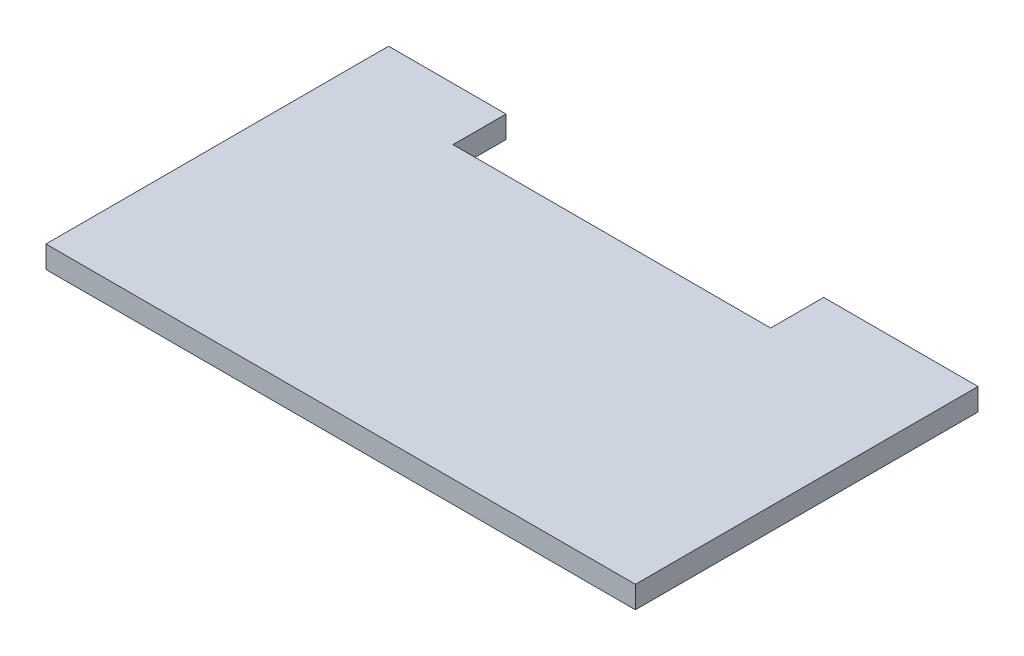
SolidWorks part; units mm, degrees
ref_plane "Front Plane" through (0, 0, 0) normal (0, 0, 1) x (1, 0, 0)
ref_plane "Top Plane" through (0, 0, 0) normal (0, 1, 0) x (1, 0, 0)
ref_plane "Right Plane" through (0, 0, 0) normal (1, 0, 0) x (0, 0, -1)
sketch "Sketch1" plane through (0, 0, 0) normal (0, 1, 0) x (1, 0, 0)
  line L0 (15.9432, 46.5) -> (15.9432, 39.3)
  line L1 (0, 0) -> (80, 0)
  line L2 (0, 0) -> (0, 46.5)
  line L3 (0, 46.5) -> (80, 46.5) construction
  line L4 (80, 0) -> (80, 46.5)
  line L5 (15.9432, 39.3) -> (59.0568, 39.3)
  line L6 (59.0568, 39.3) -> (59.0568, 46.5)
  line L7 (80, 39.3) -> (0, 39.3) construction
  line L8 (15.9432, 46.5) -> (0, 46.5)
  line L9 (59.0568, 46.5) -> (80, 46.5)
sketch "Sketch2" plane through (0, 0, 0) normal (0, 0, 1) x (1, 0, 0)
  line L1 (0, 0) -> (80, 0)
  line L2 (0, 0) -> (0, -3)
  line L3 (0, -3) -> (80, -3)
  line L4 (80, 0) -> (80, -3)
extrude "Boss-Extrude1" add sketch "Sketch1" against normal up to vertex (3 mm away) up to point (0, -3, 0)
